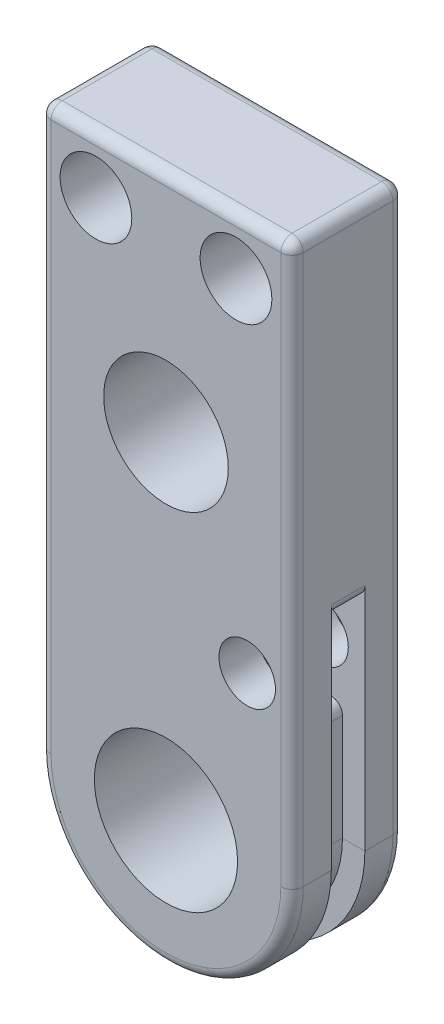
SolidWorks part; units mm, degrees
ref_plane "Front Plane" through (0, 0, 0) normal (0, 0, 1) x (1, 0, 0)
ref_plane "Top Plane" through (0, 0, 0) normal (0, 1, 0) x (1, 0, 0)
ref_plane "Right Plane" through (0, 0, 0) normal (1, 0, 0) x (0, 0, -1)
sketch "Sketch1" plane through (0, 0, 0) normal (0, 0, 1) x (1, 0, 0)
  line L0 (0, 0) -> (0, 19.05) construction
  line L3 (7.1437, 31.75) -> (7.1438, 0)
  line L7 (-7.1438, 0) -> (-7.1437, 31.75)
  line L8 (-7.1437, 31.75) -> (7.1437, 31.75)
  line L9 (-7.1437, 28.575) -> (7.1437, 28.575) construction
  line L11 (3.9687, 28.575) -> (-3.9688, 28.575)
  line L12 (4.6038, 12.3952) -> (7.1438, 12.3952)
  line L13 (4.6038, 6.6548) -> (7.1438, 6.6548)
  circle A0 centre (0, 0) radius 4.0577
  arc A1 (7.1438, 0) -> (-7.1438, 0) centre (0, 0) cw
  circle A2 centre (0, 19.05) radius 3.5306
  circle A4 centre (0, 0) radius 7.1438 construction
  circle A5 centre (-3.9688, 28.575) radius 2.032
  circle A6 centre (3.9687, 28.575) radius 2.032
  circle A7 centre (4.6038, 9.525) radius 1.6002
  arc A9 (4.6038, 12.3952) -> (4.6038, 6.6548) centre (4.6038, 9.525) ccw
  point P11 (0, 28.575)
  point P17 (0, 9.525)
  dimension "D1" = 7.1437
  dimension "D2" = 14.2875
  dimension "D3" = 7.0612
  dimension "D4" = 8.1153
  dimension "D5" = 19.05
  dimension "D6" = 180
  dimension "D13" = 1.27
  dimension "D9" = 4.064
  dimension "D10" = 4.064
  dimension "D11" = 3.2004
  dimension "D7" = 3.175
  dimension "D8" = 3.175
  dimension "D12" = 2.54
  dimension "D15" = 12.7
extrude "Boss-Extrude1" add sketch "Sketch1" along normal mid plane 6.35 contours A9 L12 L3 L8 L7 A1 L13 A6 A5 A2 A0 | L12 A9 L13 L3 A7 region at (-0.3324, 13.3751, 0) region at (7.0649, 9.525, 0)
extrude "Cut-Extrude4" cut sketch "Sketch1<7>" against normal mid plane 1.905 contours L12 A9 L13 L3 A7 region at (7.0649, 9.525, 0)
sketch "Sketch1<7>" plane through (0, 0, 0) normal (0, 0, 1) x (1, 0, 0) same geometry as "Sketch1"
sketch "Sketch3" plane through (0, 6.6548, 0) normal (0, 1, 0) x (1, 0, 0)
  line L0 (4.6038, -0.9525) -> (7.1437, -0.9525) construction
  line L1 (7.1437, 0.9525) -> (5.8737, 0.9525)
  line L2 (7.1437, 0.9525) -> (7.1437, -0.9525)
  line L3 (7.1437, -0.9525) -> (5.8737, -0.9525)
  line L4 (5.8737, 0.9525) -> (5.8737, -0.9525)
  dimension "D1" = 1.27
sketch "Sketch2" plane through (0, 0, 3.175) normal (0, 0, 1) x (1, 0, 0)
  line L0 (7.1438, 6.6548) -> (7.1438, 0)
  line L1 (7.1437, 31.75) -> (7.1438, 0) construction
  line L2 (-7.1438, 0) -> (-7.1438, 6.35)
  line L3 (-7.1438, 0) -> (-7.1437, 31.75) construction
  arc A0 (-7.1438, 0) -> (7.1438, 0) centre (0, 0) ccw construction
  arc A1 (-7.1438, 0) -> (7.1438, 0) centre (0, 0) ccw
  dimension "D1" = 6.35
sweep "Cut-Sweep1" cut profiles "Sketch3" path "Sketch2"
fillet "Fillet1" radius 0.635 10 edges at (-7.1438, 15.875, -3.175) (0, -7.1438, -3.175) (7.1437, 31.75, 0) (0, 31.75, 3.175) (-7.1437, 31.75, 0) (0, 31.75, -3.175) (7.1437, 15.875, -3.175) (0, -7.1438, 3.175) (-7.1438, 15.875, 3.175) (7.1437, 15.875, 3.175)
fillet "Fillet2" radius 0.635 4 edges at (5.8737, 6.6548, 0) (7.1437, 12.3952, 0) (-7.1437, 6.35, 0) (-5.8737, 6.35, 0)
